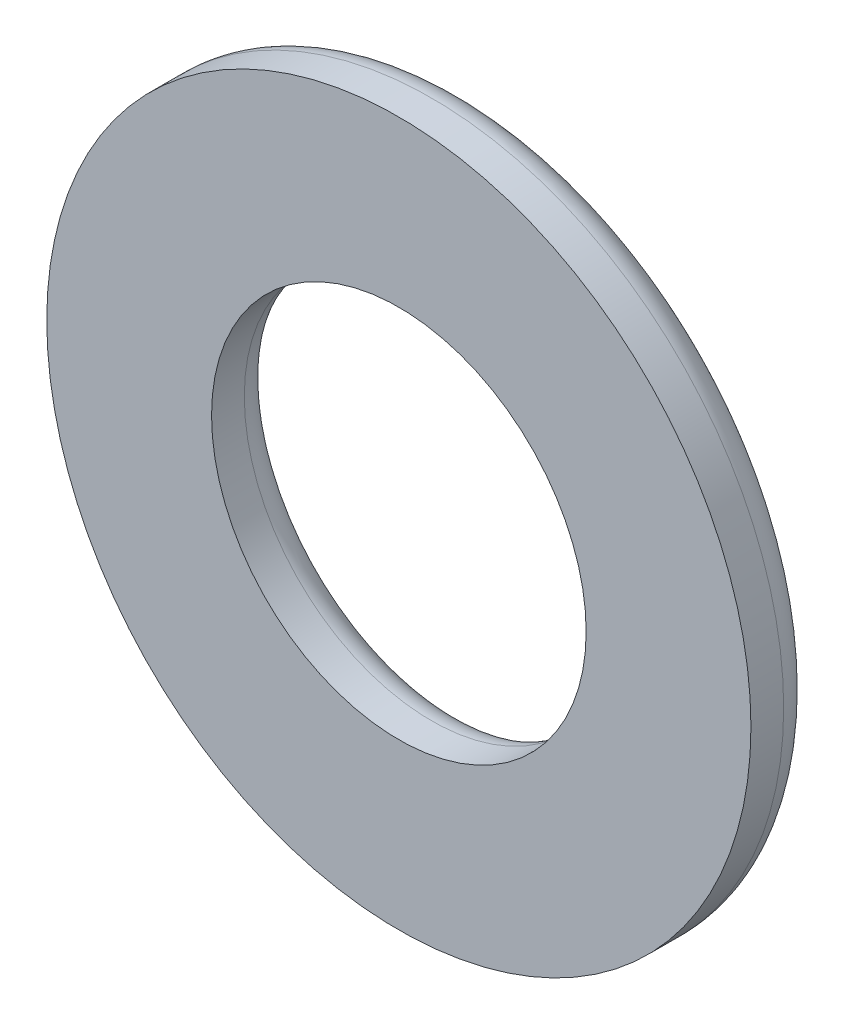
SolidWorks part; units mm, degrees
ref_plane "Front Plane" through (0, 0, 0) normal (0, 0, 1) x (1, 0, 0)
ref_plane "Top Plane" through (0, 0, 0) normal (0, 1, 0) x (1, 0, 0)
ref_plane "Right Plane" through (0, 0, 0) normal (1, 0, 0) x (0, 0, -1)
sketch "Sketch1" plane through (0, 0, 0) normal (0, 0, 1) x (1, 0, 0)
  line L0 (-6.35, 0) -> (6.35, 0) construction
  line L1 (0, 6.35) -> (0, -6.35) construction
  circle A0 centre (0, 0) radius 6.35 construction
  circle A1 centre (0, 0) radius 3.3782 construction
  point P4 (0, 0)
  point P8 (0, -3.3782)
  point P9 (3.3782, 0)
  point P10 (0, 3.3782)
  point P11 (-3.3782, 0)
  dimension "OD" = 12.7
  dimension "ID" = 6.7564
sketch "Sketch2" plane through (0, 0, 0) normal (1, 0, 0) x (0, 0, -1)
  line L0 (0.5905, 0) -> (-0.5905, 0) construction
  line L1 (0.5906, 6.35) -> (-0.5905, 6.35) construction
  line L2 (0.5906, 6.35) -> (0.5906, -6.35) construction
  line L3 (0.5906, -6.35) -> (-0.5906, -6.35) construction
  line L4 (-0.5905, 6.35) -> (-0.5906, -6.35) construction
  line L5 (-0.5905, 3.3782) -> (0.5905, 3.3782) construction
  line L6 (-0.5905, -3.3782) -> (0.5905, -3.3782) construction
  line L7 (-0.6477, 0) -> (0.6477, 0) construction
  line L8 (0, 6.35) -> (0, -6.35) construction
  point P6 (0, 0)
  point P17 (0, 0)
  point P18 (-0.5334, 0)
  point P21 (0.5334, 0)
  dimension "Max Thickness Range" = 1.2954
  dimension "Min Thickness Range" = 1.0668
  dimension "Thickness Range" = 1.1811
sketch "Sketch3" plane through (0, 0, 0) normal (0, 0, 1) x (1, 0, 0)
  line L0 (-6.35, 0) -> (6.35, 0) construction
  circle A0 centre (0, 0) radius 6.35
  circle A1 centre (0, 0) radius 3.3782
  circle A2 centre (0, 0) radius 6.35 construction
  circle A3 centre (0, 0) radius 3.3782 construction
extrude "Boss-Extrude1" add sketch "Sketch3" along normal up to vertex (0.5906 mm away) and the other way up to vertex (0.5906 mm away) up to point (0, 0, 0.5905) other way up to point (0, 0, -0.5905)
fillet "Fillet1" radius 0.5906 2 edges at (6.35, 0, -0.5905) (3.3782, 0, -0.5905)
equation "\"D1@Fillet1\" = \"Thickness Range@Sketch2\" * .5"
